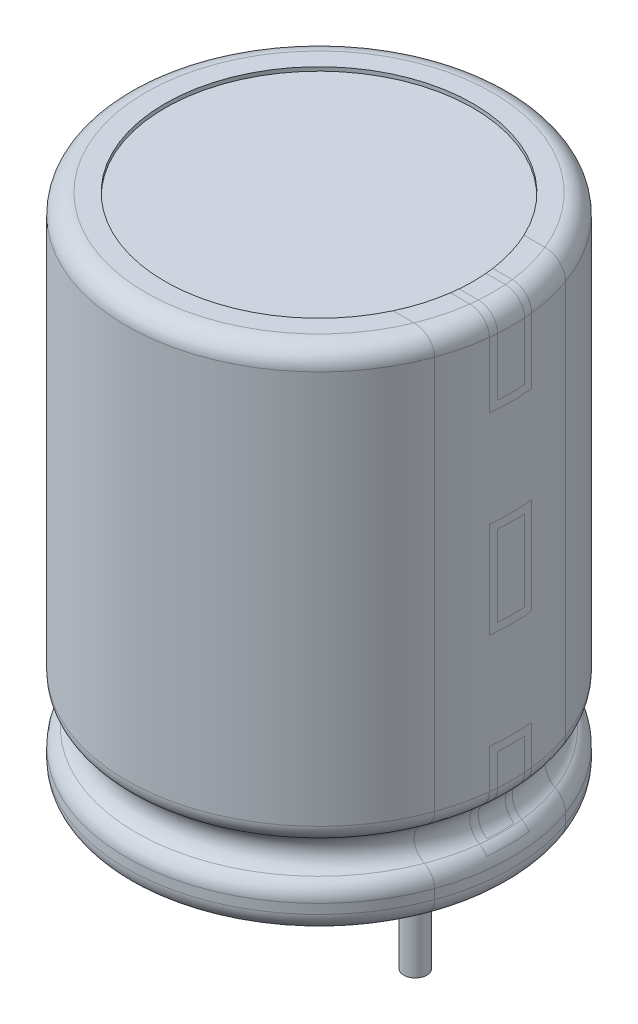
SolidWorks part; units mm, degrees
ref_plane "Front Plane" through (0, 0, 0) normal (0, 0, 1) x (1, 0, 0)
ref_plane "Top Plane" through (0, 0, 0) normal (0, 1, 0) x (1, 0, 0)
ref_plane "Right Plane" through (0, 0, 0) normal (1, 0, 0) x (0, 0, -1)
sketch "Sketch1" plane through (0, 0, 0) normal (0, 1, 0) x (1, 0, 0)
  line L0 (0, 0) -> (0, 44.7542) construction
  line L1 (0, 0) -> (-44.7542, 0) construction
  circle A0 centre (-2.5, 0) radius 0.3
  circle A1 centre (2.5, 0) radius 0.3
  dimension "D3" = 0.6
  dimension "D1" = 2.5
extrude "Boss-Extrude1" add sketch "Sketch1" against normal blind 3 and the other way blind 1
sketch "Sketch3" plane through (0, 0, 0) normal (0, 0, 1) x (1, 0, 0)
  line L1 (0, 0.1) -> (0, 13.2) construction
  line L2 (5, 0.5) -> (5, 0.75)
  line L3 (0, 0.1) -> (4, 0.1)
  line L4 (4, 13.2) -> (4.5, 13.2)
  line L5 (4, 0) -> (4.5, 0)
  line L6 (0, 13.1) -> (4, 13.1)
  line L7 (5, 2.4821) -> (5, 12.7)
  line L8 (4, 13.1) -> (4, 13.2)
  line L9 (5, 2.4821) -> (5, 13.2) construction
  line L10 (4, 0) -> (4, 0.1)
  line L11 (0, 13.1) -> (5, 13.1) construction
  line L12 (0, 13.2) -> (5, 13.2) construction
  line L13 (4, 2.4821) -> (4, 13.2) construction
  line L14 (0, 0.1) -> (0, 13.1)
  line L17 (0, 0.1) -> (5, 0.1) construction
  line L18 (0, 0) -> (5, 0) construction
  arc A0 (4.75, 2.049) -> (4.75, 1.183) centre (5, 1.616) ccw
  arc A1 (5, 0.75) -> (4.75, 1.183) centre (4.5, 0.75) ccw
  arc A2 (5, 2.4821) -> (4.75, 2.049) centre (4.5, 2.4821) cw
  arc A3 (5, 12.7) -> (4.5, 13.2) centre (4.5, 12.7) ccw
  arc A4 (4.5, 0) -> (5, 0.5) centre (4.5, 0.5) ccw
  point P13 (5, 2.116)
  point P29 (0, 20.1)
  point P30 (0, 0.1126)
  point P31 (0.1319, 0.1)
  point P32 (4.5, 1.616)
  point P33 (0.118, 20.2)
  point P35 (0, 0)
  point P36 (0.1461, 20.2)
  point P37 (-8.5502, 0.1)
  dimension "D2" = 0.5
  dimension "D1" = 0.5
  dimension "D9" = 0.5
  dimension "D3" = 13
  dimension "D6" = 5
  dimension "D7" = 0.1
  dimension "D8" = 8
  dimension "D10" = 0.25
  dimension "D11" = 9
  dimension "D5" = 1
revolve "Revolve1" add sketch "Sketch3" angle 360 about L14
sketch "Sketch4" plane through (0, 0, 0) normal (1, 0, 0) x (0, 0, -1)
  line L0 (-4.5, 0) -> (4.5, 0) construction
  line L1 (-1.7, 0) -> (1.7, 0)
  line L2 (0, 0) -> (0, 13.2) construction
  line L3 (-1.7, 13.2) -> (1.7, 13.2)
  line L4 (1.7, 0) -> (1.7, 13.2)
  line L5 (4, 13.2) -> (-4, 13.2) construction
  line L6 (-1.7, 0) -> (-1.7, 13.2)
  line L7 (-0.35, 13.3) -> (-0.35, 11.2)
  line L8 (-0.35, 13.3) -> (0.35, 13.3)
  line L9 (0, 13.3) -> (0, 11.2) construction
  line L10 (-0.35, 11.2) -> (0.35, 11.2)
  line L11 (0.35, 13.3) -> (0.35, 11.2)
  line L12 (0.55, 13.5) -> (0.55, 11)
  line L13 (-0.55, 11) -> (0.55, 11)
  line L14 (-0.55, 13.5) -> (-0.55, 11)
  line L15 (-0.55, 13.5) -> (0.55, 13.5)
  line L16 (0, 0) -> (0, -3.7489) construction
  line L17 (-0.35, 8.3) -> (-0.35, 6.2)
  line L18 (-0.35, 8.3) -> (0.35, 8.3)
  line L19 (-0.35, 6.2) -> (0.35, 6.2)
  line L20 (0.35, 8.3) -> (0.35, 6.2)
  line L21 (0.55, 8.5) -> (0.55, 6)
  line L22 (-0.55, 6) -> (0.55, 6)
  line L23 (-0.55, 8.5) -> (-0.55, 6)
  line L24 (-0.55, 8.5) -> (0.55, 8.5)
  line L25 (0, 8.3) -> (0, 6.2) construction
  line L26 (-0.35, 3.3) -> (-0.35, 1.2)
  line L27 (-0.35, 3.3) -> (0.35, 3.3)
  line L28 (-0.35, 1.2) -> (0.35, 1.2)
  line L29 (0.35, 3.3) -> (0.35, 1.2)
  line L30 (0.55, 3.5) -> (0.55, 1)
  line L31 (-0.55, 1) -> (0.55, 1)
  line L32 (-0.55, 3.5) -> (-0.55, 1)
  line L33 (-0.55, 3.5) -> (0.55, 3.5)
  line L34 (0, 3.3) -> (0, 1.2) construction
  line L35 (-0.55, 18.5) -> (0.55, 18.5)
  line L36 (-0.55, 18.5) -> (-0.55, 16)
  line L37 (-0.35, 18.3) -> (0.35, 18.3)
  line L38 (0.35, 18.3) -> (0.35, 16.2)
  line L39 (0.55, 18.5) -> (0.55, 16)
  line L40 (-0.35, 18.3) -> (-0.35, 16.2)
  line L41 (-0.35, 16.2) -> (0.35, 16.2)
  line L42 (-0.55, 16) -> (0.55, 16)
  line L51 (-0.55, 11) -> (-0.55, 8.5) construction
  line L52 (-0.55, 13.5) -> (-0.55, 16) construction
  point P20 (0, 0)
  point P23 (-0.6552, 20.4867)
  point P64 (0, 18.3)
  dimension "D5" = 3.4
  dimension "D6" = 0.2
  dimension "D7" = 1.1
  dimension "D8" = 2.1
  dimension "D1" = 0.7
  dimension "D9" = 1
  dimension "D10" = 2.5
  dimension "D2" = 3
  dimension "D3" = 2
split line "Split Line1"
